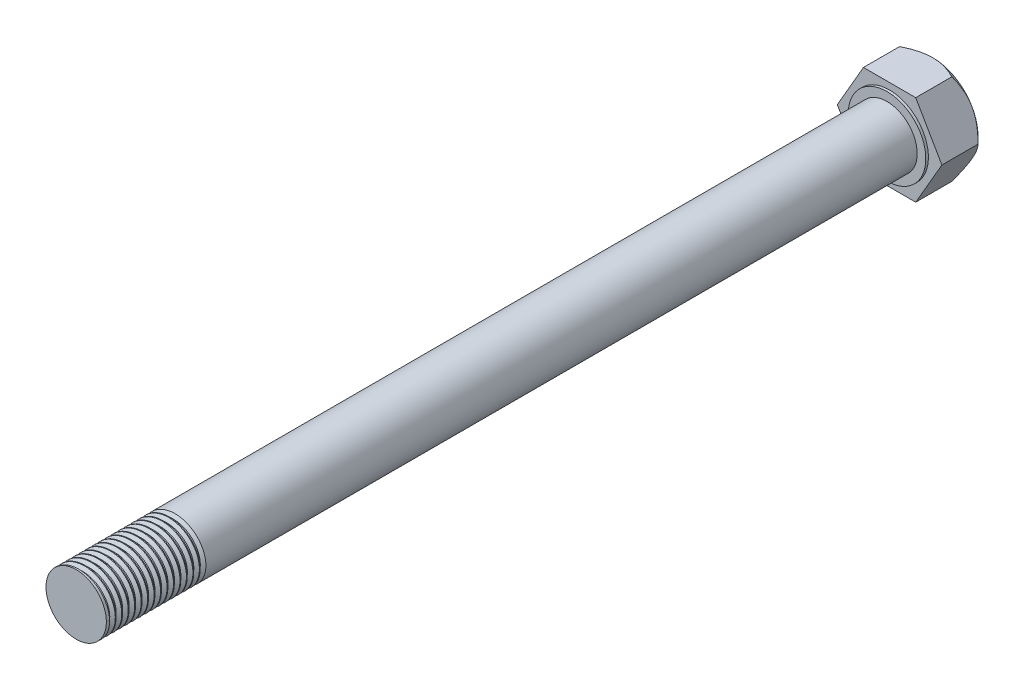
SolidWorks part; units mm, degrees
ref_plane "Front Plane" through (0, 0, 0) normal (0, 0, 1) x (1, 0, 0)
ref_plane "Top Plane" through (0, 0, 0) normal (0, 1, 0) x (1, 0, 0)
ref_plane "Right Plane" through (0, 0, 0) normal (1, 0, 0) x (0, 0, -1)
sketch "Sketch1" plane through (0, 0, 0) normal (0, 0, 1) x (1, 0, 0)
  circle A0 centre (0, 0) radius 7
  dimension "D1" = 14
extrude "Boss-Extrude1" add sketch "Sketch1" along normal blind 105 and the other way blind 83
ref_plane "Plane1" [suppressed] through (0, 0, -88) normal (0, 0, -1) x (-1, 0, 0)
sketch "Sketch2" [suppressed] plane through (0, 0, -88) normal (0, 0, -1) x (-1, 0, 0)
  line L1 (-7.5, 7.5) -> (7.5, 7.5)
  line L2 (-7.5, 7.5) -> (-7.5, -7.5)
  line L3 (-7.5, -7.5) -> (7.5, -7.5)
  line L4 (7.5, 7.5) -> (7.5, -7.5)
  line L5 (-7.5, 7.5) -> (7.5, -7.5) construction
  line L6 (-7.5, -7.5) -> (7.5, 7.5) construction
  point P0 (0, 0)
  dimension "D1" = 15
thread "Thread1" pitch 1.5 method cut profile "Thread Profile1" start angle 0, offset 0, length 22, pitch 1.5, diameter 14
ref_plane "Plane2" through (-7, 0, 105) normal (0, -1, 0) x (-1, 0, 0)
sketch "Thread Profile1" plane through (-7, 0, 105) normal (0, -1, 0) x (-1, 0, 0)
  line L0 (0, 0) -> (0, 1.5) construction
  line L11 (0, 0) -> (0, 1.3125)
  line L12 (0, 1.3125) -> (-0.8119, 0.8437)
  line L13 (-0.8119, 0.8437) -> (-0.8119, 0.4687)
  line L15 (-0.8119, 0.4687) -> (0, 0)
  line L17 (-0.8119, 0.6562) -> (0, 0.6562) construction
  point P2 (0, 0)
  dimension "Pitch" = 1.5
  dimension "Profile_Angle" = 60
  dimension "Profile_Land" = 0.375
  dimension "Profile_Height" = 0.8119
sketch "Sketch3" [suppressed] plane through (0, 0, -83) normal (0, 0, -1) x (-1, 0, 0)
  line L1 (12.1244, 0) -> (6.0622, 10.5)
  line L2 (6.0622, 10.5) -> (-6.0622, 10.5)
  line L3 (-6.0622, 10.5) -> (-12.1244, 0)
  line L4 (-12.1244, 0) -> (-6.0622, -10.5)
  line L5 (-6.0622, -10.5) -> (6.0622, -10.5)
  line L6 (6.0622, -10.5) -> (12.1244, 0)
  circle A1 centre (0, 0) radius 10.5 construction
  point P1 (0, 0)
  dimension "D1" = 21
extrude "Boss-Extrude3" [suppressed] add sketch "Sketch3" along normal blind 10
sketch "Sketch4" plane through (0, 0, -83) normal (0, 0, -1) x (-1, 0, 0)
  circle A0 centre (0, 0) radius 9
  dimension "D1" = 18
extrude "Boss-Extrude4" add sketch "Sketch4" along normal blind 0.6
sketch "Sketch5" plane through (0, 0, -83.6) normal (0, 0, -1) x (-1, 0, 0)
  line L1 (12.1244, 0) -> (6.0622, 10.5)
  line L2 (6.0622, 10.5) -> (-6.0622, 10.5)
  line L3 (-6.0622, 10.5) -> (-12.1244, 0)
  line L4 (-12.1244, 0) -> (-6.0622, -10.5)
  line L5 (-6.0622, -10.5) -> (6.0622, -10.5)
  line L6 (6.0622, -10.5) -> (12.1244, 0)
  circle A0 centre (0, 0) radius 10.5 construction
  dimension "D1" = 21
extrude "Boss-Extrude5" add sketch "Sketch5" along normal blind 10
sketch "Sketch6" plane through (0, 0, -93.6) normal (0, 0, -1) x (-1, 0, 0)
  circle A0 centre (0, 0) radius 10.5
  dimension "D1" = 21
extrude "Cut-Extrude1" cut sketch "Sketch6" against normal blind 10 draft 45 flip side to cut
